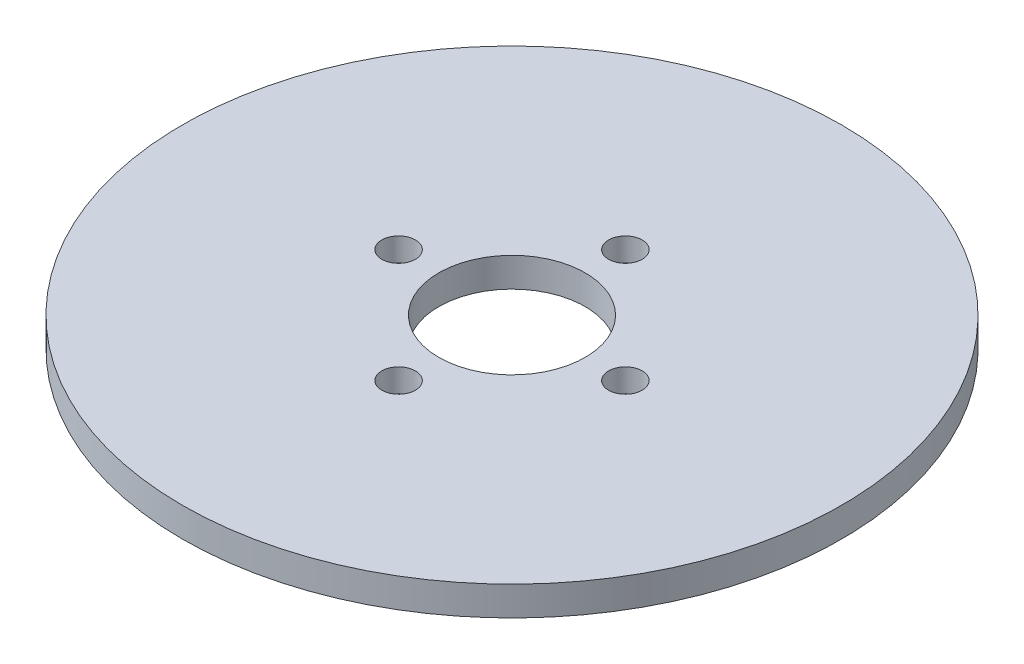
SolidWorks part; units mm, degrees
ref_plane "Front Plane" through (0, 0, 0) normal (0, 0, 1) x (1, 0, 0)
ref_plane "Top Plane" through (0, 0, 0) normal (0, 1, 0) x (1, 0, 0)
ref_plane "Right Plane" through (0, 0, 0) normal (1, 0, 0) x (0, 0, -1)
sketch "Sketch1" plane through (0, 0, 0) normal (0, 1, 0) x (1, 0, 0)
  circle A0 centre (0, 0) radius 45
  dimension "FLANGE_OD" = 90
extrude "Boss-Extrude1" add sketch "Sketch1" along normal blind 4
sketch "Sketch2" plane through (0, 0, 0) normal (0, 1, 0) x (1, 0, 0)
  circle A0 centre (0, 0) radius 10
  dimension "BORE_D" = 20
extrude "Cut-Extrude1" cut sketch "Sketch2" along normal through all
sketch "Sketch3" plane through (0, 4, 0) normal (0, 1, 0) x (1, 0, 0)
  circle A0 centre (0, 0) radius 15.4826 construction
  circle A1 centre (-15.4826, 0) radius 2.2942
  dimension "BOLT_D" = 4.5884
  dimension "BOLT_PCD" = 30.9653
extrude "Cut-Extrude2" cut sketch "Sketch3" against normal blind 3.1802
pattern_circular "CirPattern1" count 4 over 360 about axis through (0, 0, 0) along (0, 1, 0) of "Cut-Extrude2"
